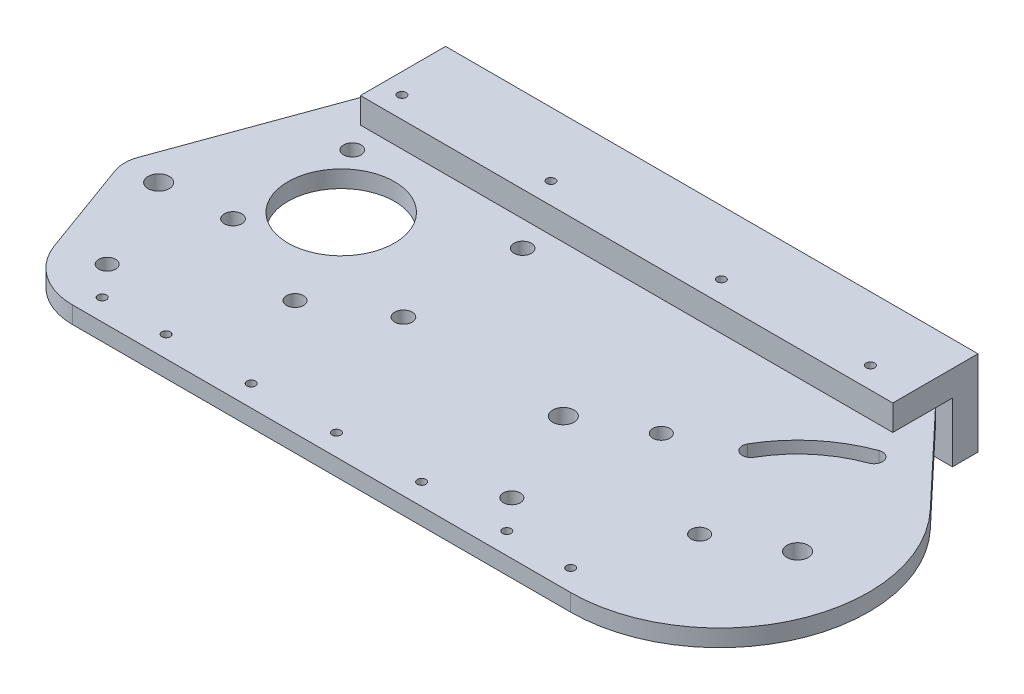
SolidWorks part; units mm, degrees
ref_plane "前视基准面" through (0, 0, 0) normal (0, 0, 1) x (1, 0, 0)
ref_plane "上视基准面" through (0, 0, 0) normal (0, 1, 0) x (1, 0, 0)
ref_plane "右视基准面" through (0, 0, 0) normal (1, 0, 0) x (0, 0, -1)
sketch "草图1" plane through (0, 0, 0) normal (0, 1, 0) x (1, 0, 0)
  line L0 (-95, 0) -> (0, 0) construction
  line L1 (0, 8.8147) -> (0, -8) construction
  line L2 (-95, 0) -> (-115, -34.641) construction
  line L3 (0, 0) -> (95, 0) construction
  line L4 (95, 0) -> (75, -34.641) construction
  line L5 (40, -8) -> (0, -8) construction
  line L6 (-102.5175, -2.7362) -> (-94.3667, -25.1303)
  line L7 (-80.2714, -35) -> (36.6801, -35)
  line L8 (-82, 29.134) -> (-129.5, -20.866) construction
  line L9 (-115, -34.641) -> (75, -34.641) construction
  line L10 (-115, -54.641) -> (75, -54.641) construction
  line L11 (-67.5, -34.641) -> (-67.5, 15.359) construction
  line L12 (-102.5175, 2.7362) -> (-88.2015, 42.0691)
  line L13 (-83.5031, 45.359) -> (42, 45.359)
  line L14 (-60.8782, 34.231) -> (81.6218, -15.769) construction
  line L15 (-88, 35.359) -> (-88, -4.641) construction
  line L16 (-88, -4.641) -> (-29.8, -4.641) construction
  line L17 (-29.8, -4.641) -> (-29.8, 35.359) construction
  line L18 (-29.8, 35.359) -> (-88, 35.359) construction
  line L19 (-67.5, 15.359) -> (-88, 15.359) construction
  line L20 (-78.9, 29.359) -> (-38.9, 29.359) construction
  line L21 (-38.9, 29.359) -> (-38.9, 1.359) construction
  line L22 (-78.9, 1.359) -> (-38.9, 1.359) construction
  line L23 (-78.9, 1.359) -> (-78.9, 29.359) construction
  line L24 (-67.5, 15.359) -> (-38.9, 15.359) construction
  line L25 (-55, -8) -> (-95, -8) construction
  line L26 (42, 45.359) -> (62.1355, 24.0212)
  line L27 (-95, -8) -> (-95, 0) construction
  line L28 (75, -34.641) -> (55, 0) construction
  line L29 (-95, 0) -> (-84.4345, -22.6577) construction
  line L30 (0, 0) -> (-15.8661, -27.4809) construction
  line L31 (0, 0) -> (10.5655, -22.6577) construction
  line L32 (55, 0) -> (40, 25.9808) construction
  line L33 (55, 0) -> (55, 8) construction
  line L34 (55, 8) -> (15, 8) construction
  line L35 (55, 0) -> (44.7394, 28.1908) construction
  line L36 (55, 0) -> (29.0192, 15) construction
  circle A0 centre (-95, 0) radius 2.5
  circle A1 centre (0, 0) radius 2.5
  circle A2 centre (-84.4345, -22.6577) radius 2
  arc A3 (-102.5175, 2.7362) -> (-102.5175, -2.7362) centre (-95, 0) ccw
  circle A4 centre (-67.5, 15.359) radius 20 construction
  circle A5 centre (-78.9, 29.359) radius 2.05
  circle A6 centre (-38.9, 29.359) radius 2.05
  arc A7 (-80.2714, -35) -> (-94.3667, -25.1303) centre (-80.2714, -20) cw
  circle A8 centre (-55, -8) radius 2
  circle A9 centre (40, -8) radius 2
  circle A10 centre (-115, -34.641) radius 20 construction
  circle A11 centre (75, -34.641) radius 20 construction
  circle A12 centre (-67.5, 15.359) radius 12.5
  circle A13 centre (-38.9, 1.359) radius 2.05
  circle A14 centre (-78.9, 1.359) radius 2.05
  arc A15 (-83.5031, 45.359) -> (-88.2015, 42.0691) centre (-83.5031, 40.359) ccw
  circle A16 centre (55, 0) radius 2.5
  arc A17 (36.6801, -35) -> (62.1355, 24.0212) centre (36.6801, 0) ccw
  circle A18 centre (10.5655, -22.6577) radius 2
  circle A19 centre (40, 25.9808) radius 2 construction
  circle A20 centre (15, 8) radius 2
  circle A21 centre (-78.2714, -30) radius 1
  circle A22 centre (-43.2714, -30) radius 1
  circle A23 centre (-3.2714, -30) radius 1
  arc A24 (45.4234, 26.3114) -> (44.0554, 30.0702) centre (44.7394, 28.1908) ccw
  arc A25 (27.2872, 16) -> (30.7513, 14) centre (29.0192, 15) ccw
  arc A26 (45.4234, 26.3114) -> (30.7513, 14) centre (55, 0) ccw
  arc A27 (46.6405, 28.8118) -> (28.0775, 13.2356) centre (55, 0) ccw construction
  arc A28 (44.0554, 30.0702) -> (27.2872, 16) centre (55, 0) ccw
  circle A29 centre (31.7286, -30) radius 1
  circle A30 centre (-78.2714, 40.359) radius 1
  circle A31 centre (-43.2714, 40.359) radius 1
  circle A32 centre (-3.2714, 40.359) radius 1
  circle A33 centre (31.7286, 40.359) radius 1
  circle A34 centre (-63.2714, -30) radius 1
  circle A35 centre (-23.2714, -30) radius 1
  circle A36 centre (16.7286, -30) radius 1
  circle A37 centre (-63.2714, 40.359) radius 1
  circle A38 centre (-23.2714, 40.359) radius 1
  circle A39 centre (16.7286, 40.359) radius 1
  dimension "D1" = 5
  dimension "D3" = 16
  dimension "D6" = 95
  dimension "D7" = 15
  dimension "D8" = 4
  dimension "D9" = 8
  dimension "D10" = 40
  dimension "D13" = 40
  dimension "D18" = 25
  dimension "D11" = 40
  dimension "D25" = 4.1
  dimension "D28" = 5
  dimension "D31" = 25
  dimension "D33" = 4
  dimension "D37" = 4
  dimension "D39" = 2
  dimension "D43" = 30
  dimension "D44" = 28
  dimension "D45" = 32
  dimension "D46" = 2
  dimension "D48" = 5
  dimension "D49" = 2
  dimension "D50" = 35
  dimension "D51" = 40
  dimension "D52" = 35
  dimension "D53" = 2
  dimension "D54" = 5
  dimension "D55" = 15
  dimension "D59" = 20
  dimension "D60" = 15
  dimension "D34" = 35
  dimension "D62" = 35
  dimension "D4" = 70
  dimension "D5" = 35
  dimension "D12" = 190
  dimension "D14" = 60
  dimension "D15" = 40
  dimension "D16" = 50
  dimension "D17" = 47.5
  dimension "D19" = 40
  dimension "D20" = 58.2
  dimension "D21" = 20.5
  dimension "D22" = 9.1
  dimension "D23" = 28
  dimension "D24" = 40
  dimension "D26" = 20
  dimension "D27" = 110
  dimension "D29" = 130
  dimension "D30" = 25
  dimension "D32" = 60
  dimension "D35" = 25
  dimension "D36" = 25
  dimension "D38" = 30
  dimension "D40" = 8
  dimension "D41" = 30
  dimension "D42" = 10
  dimension "D47" = 2
  dimension "D61" = 40
  dimension "D56" = 2
  dimension "D57" = 2
  dimension "D58" = 2
extrude "凸台-拉伸1" add sketch "草图1" along normal mid plane 4
scale "Scale1" scale about centroid uniform scaling yes scale factor 2
ref_plane "Plane1" through (98.7018, -4, -86.6963) normal (-1, 0, 0) x (0, 0, 1)
sketch "Sketch4" plane through (98.7018, -4, -86.6963) normal (-1, 0, 0) x (0, 0, 1)
  line L0 (-8, 0) -> (20, 0)
  line L1 (20, 0) -> (20, -12)
  line L2 (20, -12) -> (-20, -12)
  line L3 (-20, -12) -> (-20, 28)
  line L4 (-20, 28) -> (-8, 28)
  line L5 (-8, 0) -> (-8, 28)
  dimension "D1" = 12
  dimension "D2" = 40
  dimension "D3" = 20
  dimension "D4" = 12
  dimension "D5" = 40
extrude "Extrude2" add sketch "Sketch4" along normal blind 250
sketch "Sketch5" plane through (0, -16, 0) normal (0, -1, 0) x (1, 0, 0)
  circle A0 centre (8.1591, -76.6963) radius 2 construction
  circle A1 centre (-71.8409, -76.6963) radius 2 construction
  circle A2 centre (78.1591, -76.6963) radius 2 construction
  circle A3 centre (-141.8409, -76.6963) radius 2 construction
  circle A4 centre (8.1591, -76.6963) radius 2
  circle A5 centre (-71.8409, -76.6963) radius 2
  circle A6 centre (78.1591, -76.6963) radius 2
  circle A7 centre (-141.8409, -76.6963) radius 2
extrude "Extrude3" cut sketch "Sketch5" against normal through all
sketch "Sketch6" plane through (0, 0, -106.6963) normal (0, 0, -1) x (-1, 0, 0)
  line L0 (151.2982, 24) -> (-98.7018, 24) construction
  circle A0 centre (-79.0063, 9) radius 2
  circle A1 centre (-9.0598, 9) radius 2
  circle A2 centre (73.3433, 9) radius 2
  circle A3 centre (141.789, 9) radius 2
  dimension "D1" = 4
  dimension "D2" = 15
extrude "Extrude4" cut sketch "Sketch6" against normal through all
ref_plane "Plane2" through (0, 0, -6.3373) normal (0, 0, -1) x (-1, 0, 0)
ref_plane "Plane3" through (0, 0, 0) normal (0, -1, 0) x (-1, 0, 0)
mirror "Mirror4" about plane through (0, 0, 0) normal (0, -1, 0) of "Extrude4", "Extrude3", "Extrude2"
sketch "Sketch8" plane through (0, 0, -94.6963) normal (0, 0, 1) x (1, 0, 0)
  line L1 (-162.0674, 16) -> (123.2698, 16)
  line L2 (-162.0674, 16) -> (-162.0674, 46.4154)
  line L3 (-162.0674, 46.4154) -> (123.2698, 46.4154)
  line L4 (123.2698, 16) -> (123.2698, 46.4154)
extrude "Extrude5" cut sketch "Sketch8" against normal through all
sketch "Sketch9" plane through (0, -16, 0) normal (0, -1, 0) x (1, 0, 0)
  line L1 (-156.0799, -94.6963) -> (115.842, -94.6963)
  line L2 (-156.0799, -94.6963) -> (-156.0799, -58.9399)
  line L3 (-156.0799, -58.9399) -> (115.842, -58.9399)
  line L4 (115.842, -94.6963) -> (115.842, -58.9399)
extrude "Extrude6" cut sketch "Sketch9" against normal up to surface (12 mm away) up to face at (48.1591, -4, 66.0217)
